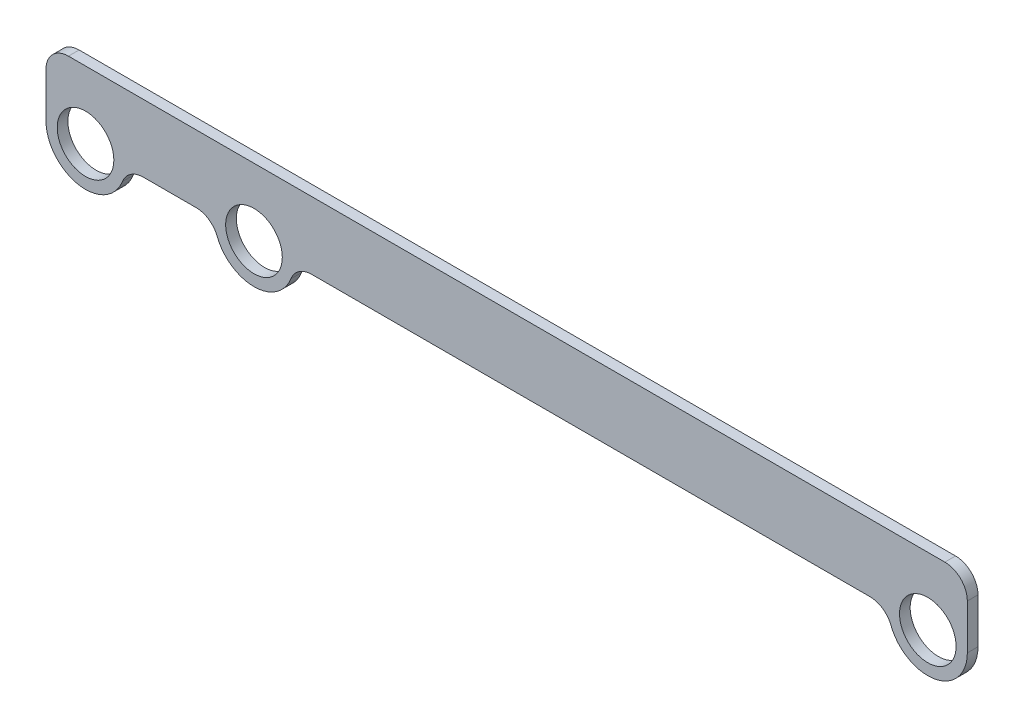
SolidWorks part; units mm, degrees
material "ASTM A36 Aço"
ref_plane "Plano frontal" through (0, 0, 0) normal (0, 0, 1) x (1, 0, 0)
ref_plane "Plano superior" through (0, 0, 0) normal (0, 1, 0) x (1, 0, 0)
ref_plane "Plano direito" through (0, 0, 0) normal (1, 0, 0) x (0, 0, -1)
sketch "Esboço2" plane through (0, 0, 0) normal (0, 0, 1) x (1, 0, 0)
  line L0 (410.3361, -12.8083) -> (410.3361, 47.1917)
  line L1 (410.3361, 47.1917) -> (-410.0639, 47.1917)
  line L2 (-410.0639, 47.1917) -> (-410.0639, -12.8083)
  line L3 (-339.6639, -12.8083) -> (-260.0639, -12.8083)
  line L4 (-189.6639, -12.8083) -> (339.9361, -12.8083)
  circle A0 centre (375.1361, -12.8083) radius 25.2
  arc A1 (339.9361, -12.8083) -> (410.3361, -12.8083) centre (375.1361, -12.8083) ccw
  circle A2 centre (-224.8639, -12.8083) radius 25.2
  arc A3 (-260.0639, -12.8083) -> (-189.6639, -12.8083) centre (-224.8639, -12.8083) ccw
  circle A4 centre (-374.8639, -12.8083) radius 25.2
  arc A5 (-410.0639, -12.8083) -> (-339.6639, -12.8083) centre (-374.8639, -12.8083) ccw
  dimension "D1" = 50.4
base flange "Flange-base1" sketch "Esboço2" thickness 9.5 reverse thickness direction no parameters "D1"=1
fillet "Filete1" radius 20 6 edges at (339.9361, -12.8083, -4.75) (-189.6639, -12.8083, -4.75) (-260.0639, -12.8083, -4.75) (-339.6639, -12.8083, -4.75) (410.3361, 47.1917, -4.75) (-410.0639, 47.1917, -4.75)
ref_plane "Plano1" through (0, 0, -4.75) normal (0, 0, 1) x (1, 0, 0)
sketch "Esboço7" plane through (0, 0, -4.75) normal (0, 0, 1) x (1, 0, 0)
  line L0 (-374.8639, -12.8083) -> (-374.8639, -99.572) construction
  line L1 (-224.8639, -12.8083) -> (-224.8639, -99.572) construction
  line L2 (375.1361, -12.8083) -> (375.1361, -99.572) construction
  dimension "D1" = 150
  dimension "D2" = 600
sketch "Curva-Linhas1" [suppressed] plane through (0, 0, 0) normal (0, 1, 0) x (1, 0, 0)
sketch "Caixa delimitadora1" [suppressed] plane through (0, 0, 0) normal (0, 1, 0) x (1, 0, 0)
sheet metal parameters "Chapa metálica1" thickness 9.5 parameters "D1"=1
flat pattern "Padrão-Plano1" [suppressed]
sketch "Curva-Linhas2" plane through (0, 0, 0) normal (0, 1, 0) x (1, 0, 0)
sketch3d "Caixa delimitadora2" [suppressed]
  line L0 (-785.2, -35.2, 0) -> (35.2, -35.2, 0) construction
  line L1 (-785.2, 60, 0) -> (35.2, 60, 0) construction
  line L2 (-785.2, -35.2, 0) -> (-785.2, 60, 0) construction
  line L3 (35.2, -35.2, 0) -> (35.2, 60, 0) construction
